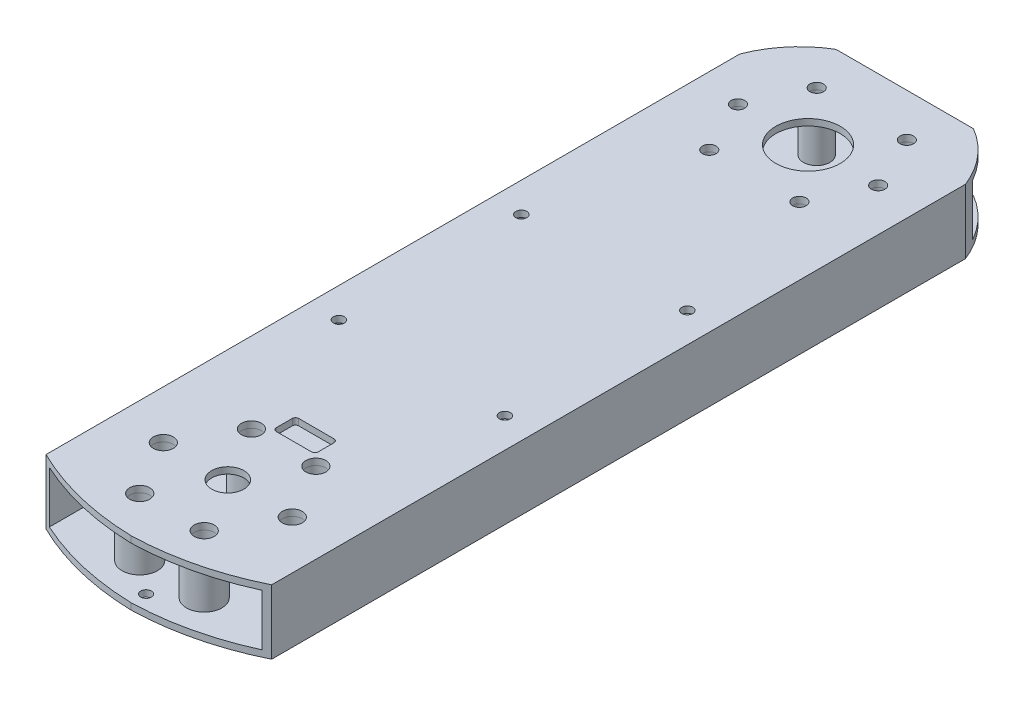
SolidWorks part; units mm, degrees
material "6061-T4 (SS)"
ref_plane "前视基准面" through (0, 0, 0) normal (0, 0, 1) x (1, 0, 0)
ref_plane "上视基准面" through (0, 0, 0) normal (0, 1, 0) x (1, 0, 0)
ref_plane "右视基准面" through (0, 0, 0) normal (1, 0, 0) x (0, 0, -1)
sketch "草图1" plane through (0, 0, 0) normal (0, 0, 1) x (1, 0, 0)
  line L0 (-33, 8) -> (-33, -8)
  line L1 (-35, 10) -> (35, 10)
  line L2 (-35, 10) -> (-35, -10)
  line L3 (-35, -10) -> (35, -10)
  line L4 (35, 10) -> (35, -10)
  line L5 (-35, 10) -> (35, -10) construction
  line L6 (-35, -10) -> (35, 10) construction
  line L7 (-33, -8) -> (33, -8)
  line L8 (33, 8) -> (33, -8)
  line L9 (-33, 8) -> (33, 8)
  point P0 (0, 0)
  dimension "D1" = 20
  dimension "D2" = 70
  dimension "D3" = 2
extrude "凸台-拉伸1" add sketch "草图1" along normal blind 240
sketch "草图2" plane through (0, 10, 0) normal (0, 1, 0) x (1, 0, 0)
  line L0 (35, 0) -> (-35, 0) construction
  circle A0 centre (0, -30) radius 10
  dimension "D1" = 20
  dimension "D2" = 30
extrude "切除-拉伸1" cut sketch "草图2" against normal up to next
sketch "草图3" plane through (0, 10, 0) normal (0, 1, 0) x (1, 0, 0)
  circle A0 centre (0, -210) radius 5
  circle A1 centre (0, -30) radius 10 construction
  dimension "D1" = 180
  dimension "D2" = 10
extrude "切除-拉伸2" cut sketch "草图3" against normal up to next
sketch "草图4" plane through (0, 10, 0) normal (0, 1, 0) x (1, 0, 0)
  line L0 (-13.9806, -13.3385) -> (0, -30) construction
  line L1 (0, -11) -> (0, 11) construction
  line L2 (13.9806, -13.3385) -> (0, -30) construction
  line L3 (0, -30) -> (14.9626, -30) construction
  circle A0 centre (0, -30) radius 21.75 construction
  circle A1 centre (-13.9806, -13.3385) radius 2.1
  circle A2 centre (-21.75, -30) radius 2.1
  circle A3 centre (13.9806, -13.3385) radius 2.1
  circle A4 centre (21.75, -30) radius 2.1
  circle A5 centre (13.9806, -46.6615) radius 2.1
  circle A6 centre (-13.9806, -46.6615) radius 2.1
  dimension "D1" = 43.5
  dimension "D3" = 4.2
  dimension "D2" = 80
extrude "切除-拉伸3" cut sketch "草图4" against normal through all
sketch "草图7" plane through (0, -10, 0) normal (0, -1, 0) x (1, 0, 0)
  line L0 (-35, 240) -> (-35, 0) construction
  line L1 (-35, 0) -> (35, 0) construction
  line L2 (-35, 16.1803) -> (-35, 0)
  line L3 (-35, 0) -> (-21.3082, 0)
  line L4 (0, -11) -> (0, 11) construction
  line L5 (35, 16.1803) -> (35, 0)
  line L6 (35, 0) -> (21.3082, 0)
  arc A0 (-35, 16.1803) -> (-21.3082, 0) centre (-4.9317, 27.741) ccw
  arc A1 (35, 16.1803) -> (21.3082, 0) centre (4.9317, 27.741) cw
extrude "切除-拉伸5" cut sketch "草图7" against normal up to next
sketch "草图10" plane through (0, 10, 0) normal (0, 1, 0) x (1, 0, 0)
  line L0 (-35, -240) -> (-35, -16.1803) construction
  line L1 (35, -240) -> (-35, -240) construction
  line L2 (-35, -231.3969) -> (-35, -240)
  line L3 (-35, -240) -> (35, -240)
  line L4 (0, -11) -> (0, 11) construction
  line L5 (35, -231.3969) -> (35, -240)
  arc A0 (-35, -231.3969) -> (0, -240) centre (2.0788, -156.0456) ccw
  arc A1 (35, -231.3969) -> (0, -240) centre (-2.0788, -156.0456) cw
  line M16 (-35, -16.1803) -> (-35, -240)
  line M17 (-35, -240) -> (35, -240)
  line M18 (35, -240) -> (35, -16.1803)
extrude "切除-拉伸8" cut sketch "草图10" against normal through all contours A0 M16 M17 | A1 L3 M18 region at (-25.9053, 10, 237.4389) region at (25.9053, 10, 237.4389)
sketch "草图13" plane through (0, 10, 0) normal (0, 1, 0) x (1, 0, 0)
  circle A0 centre (0, -210) radius 20 construction
  circle A1 centre (-20, -210) radius 3.1
  circle A2 centre (-10, -192.6795) radius 3.1
  circle A3 centre (10, -192.6795) radius 3.1
  circle A4 centre (20, -210) radius 3.1
  circle A5 centre (10, -227.3205) radius 3.1
  circle A6 centre (-10, -227.3205) radius 3.1
  point P17 (0, -210)
  dimension "D1" = 40
  dimension "D2" = 6.2
  dimension "D3" = 6
extrude "切除-拉伸10" cut sketch "草图13" against normal through all
sketch "草图14" plane through (0, 10, 0) normal (0, 1, 0) x (1, 0, 0)
  line L1 (-6.5, -182.5) -> (6.5, -182.5)
  line L2 (-6.5, -182.5) -> (-6.5, -189.5)
  line L3 (-6.5, -189.5) -> (6.5, -189.5)
  line L4 (6.5, -182.5) -> (6.5, -189.5)
  circle A0 centre (0, -210) radius 5 construction
  point P4 (0, -210)
  point P5 (-6.5, -186)
  point P9 (0, -189.5)
  dimension "D1" = 13
  dimension "D2" = 7
  dimension "D3" = 24
extrude "切除-拉伸11" cut sketch "草图14" against normal up to next
fillet "圆角1" radius 1 4 edges at (6.5, 9, 189.5) (-6.5, 9, 189.5) (6.5, 9, 182.5) (-6.5, 9, 182.5)
ref_axis "基准轴1" through (0, 0, 0) along (0, 0, -1)
sketch "草图15" plane through (0, -10, 0) normal (0, -1, 0) x (1, 0, 0)
  line L0 (-19.4178, 184.3644) -> (-7.8462, 179.841) construction
  line L1 (-7.8462, 179.841) -> (-17.7624, 171.5366) construction
  line L2 (-17.7624, 171.5366) -> (-19.4178, 184.3644) construction
  line L3 (0, 172.4773) -> (-11.4229, 159.2226) construction
  line L4 (-11.4229, 159.2226) -> (-9.9335, 152.7685) construction
  line L5 (-9.9335, 152.7685) -> (9.9335, 152.7685) construction
  line L8 (-16.8218, 85.3147) -> (-13.0628, 86.976) construction
  line L9 (-13.0628, 86.976) -> (-8.8371, 80.5314) construction
  line L10 (-8.8371, 80.5314) -> (-13.9282, 77.1933) construction
  line L11 (-13.9282, 77.1933) -> (-16.8218, 85.3147) construction
  line L12 (0, 76.7339) -> (-13.644, 67.7877) construction
  line L13 (-13.644, 67.7877) -> (0, 55.5925) construction
  line L16 (0, -11) -> (0, 11) construction
  line L17 (7.8462, 179.841) -> (17.7624, 171.5366) construction
  line L18 (19.4178, 184.3644) -> (7.8462, 179.841) construction
  line L19 (17.7624, 171.5366) -> (19.4178, 184.3644) construction
  line L20 (8.8371, 80.5314) -> (13.9282, 77.1933) construction
  line L21 (13.0628, 86.976) -> (8.8371, 80.5314) construction
  line L22 (16.8218, 85.3147) -> (13.0628, 86.976) construction
  line L23 (13.9282, 77.1933) -> (16.8218, 85.3147) construction
  line L24 (13.644, 67.7877) -> (0, 55.5925) construction
  line L25 (0, 76.7339) -> (13.644, 67.7877) construction
  line L26 (11.4229, 159.2226) -> (9.9335, 152.7685) construction
  line L27 (0, 172.4773) -> (11.4229, 159.2226) construction
  circle A0 centre (0, 30) radius 1
  circle A1 centre (0, 30) radius 10 construction
  point P33 (0, 152.7685)
  dimension "D1" = 2
extrude "切除-拉伸12" cut sketch "草图15" against normal up to next
sketch "草图16" plane through (0, -10, 0) normal (0, -1, 0) x (1, 0, 0)
  circle A0 centre (-10, 227.3205) radius 5
  circle A1 centre (10, 227.3205) radius 5
  circle A2 centre (20, 210) radius 5
  circle A3 centre (10, 192.6795) radius 5
  circle A4 centre (-10, 192.6795) radius 5
  circle A5 centre (-20, 210) radius 5
  circle A6 centre (0, 210) radius 1
  dimension "D1" = 10
  dimension "D2" = 2
hole_wizard "M3 螺纹孔1" positions "3D草图1" profile "草图19" tap size "M3" standard "GB" end condition up to next
sketch3d "3D草图1"
  circle A0 centre (0, -10, 30) radius 1 construction
  circle A1 centre (0, -10, 210) radius 1 construction
  point P0 (0, -10, 30)
  point P6 (0, -11, 30)
  point P7 (0, -10, 210)
  point P12 (0, -11, 210)
sketch "草图19" plane through (0, -10, 30) normal (1, 0, 0) x (0, 0, -1)
  line L0 (0, 0) -> (0, 20)
  line L1 (0, 20) -> (1.25, 20)
  line L2 (1.25, 20) -> (1.25, 0)
  line L5 (1.25, 0) -> (0, 0)
  line L11 (0, -6.35) -> (0, 107.95) construction
  dimension "通孔螺纹孔钻头直径" = 2.5
  dimension "通孔螺纹孔钻头深度" = 20
cosmetic thread "孔螺蚊线1" parameters "D2"=3
cosmetic thread "孔螺蚊线2" parameters "D2"=3
ref_axis "基准轴2" through (0, -8, 30) along (0, -1, 0)
ref_plane "基准面1" through (0, 0, 0) normal (1, 0, 0) x (0, -1, 0)
sketch "草图40" plane through (0, -10, 0) normal (0, -1, 0) x (1, 0, 0)
  line L0 (0, -1.1) -> (0, 1.1) construction
  line L1 (-21.3082, 0) -> (21.3082, 0) construction
  circle A0 centre (-4, 20) radius 1.7
  circle A1 centre (4, 20) radius 1.7
  dimension "D1" = 3.4
  dimension "D2" = 8
  dimension "D3" = 20
extrude "切除-拉伸21" cut sketch "草图40" against normal blind 10
sketch "草图45" plane through (35, 0, 0) normal (1, 0, 0) x (0, 0, -1)
  line L0 (-231, 8) -> (-204, -10)
  line L2 (-240, 8) -> (-240, 10) construction
  line L3 (-240, -10) -> (-240, -8) construction
  line L4 (-240, 8) -> (-231, 8)
  line L5 (-204, -10) -> (-240, -10)
  line L6 (-240, -10) -> (-240, 8)
  dimension "D1" = 9
  dimension "D2" = 36
extrude "偷轻" [suppressed] cut sketch "草图45" against normal through all
sketch "草图46" [suppressed] plane through (0, -10, 0) normal (0, -1, 0) x (-1, 0, 0)
  line L0 (33, -207) -> (11.9465, -187.6795)
  line L1 (11.9465, -187.6795) -> (-11.9465, -187.6795)
  line L2 (-11.9465, -187.6795) -> (-33, -207)
  line L3 (35, -204) -> (-35, -204) construction
  line L4 (33, -207) -> (-33, -207)
  circle A0 centre (-10, -192.6795) radius 5 construction
  circle A1 centre (-10, -192.6795) radius 5 construction
  circle A2 centre (10, -192.6795) radius 5 construction
  circle A3 centre (10, -192.6795) radius 5 construction
  point P9 (0, -204)
  point P10 (0, -187.6795)
extrude "切除-拉伸26" [suppressed] cut sketch "草图46" against normal up to next
fillet "圆角5" [suppressed] radius 6
sketch "草图49" plane through (0, 8, 0) normal (0, -1, 0) x (1, 0, 0)
  line L0 (0, -1.1) -> (0, 1.1) construction
  circle A0 centre (-13.9806, 46.6615) radius 4.1
  circle A1 centre (-13.9806, 46.6615) radius 2.2
  circle A2 centre (-21.75, 30) radius 2.2
  circle A3 centre (-21.75, 30) radius 4.1
  circle A4 centre (-13.9806, 13.3385) radius 4.1
  circle A5 centre (-13.9806, 13.3385) radius 2.2
  circle A6 centre (13.9806, 13.3385) radius 2.2
  circle A7 centre (13.9806, 13.3385) radius 4.1
  circle A8 centre (21.75, 30) radius 4.1
  circle A9 centre (21.75, 30) radius 2.2
  circle A10 centre (13.9806, 46.6615) radius 2.2
  circle A11 centre (13.9806, 46.6615) radius 4.1
  circle A12 centre (-10, 227.3205) radius 3.2
  circle A13 centre (-10, 227.3205) radius 5.5
  circle A14 centre (10, 227.3205) radius 5.5
  circle A15 centre (10, 227.3205) radius 3.2
  circle A16 centre (20, 210) radius 5.5
  circle A17 centre (20, 210) radius 3.2
  circle A18 centre (10, 192.6795) radius 5.5
  circle A19 centre (10, 192.6795) radius 3.2
  circle A20 centre (-10, 192.6795) radius 5.5
  circle A21 centre (-10, 192.6795) radius 3.2
  circle A22 centre (-20, 210) radius 5.5
  circle A23 centre (-20, 210) radius 3.2
  circle A24 centre (10, 227.3205) radius 3.1 construction
  point P44 (0, 210)
  dimension "D1" = 4.4
  dimension "D2" = 8.2
  dimension "D3" = 6.4
  dimension "D4" = 11
  dimension "D5" = 6
extrude "凸台-拉伸2" add sketch "草图49" along normal up to surface (16 mm away) up to face at (-4, -8, 21.7)
sketch "草图50" plane through (0, 10, 0) normal (0, 1, 0) x (1, 0, 0)
  circle A0 centre (-25.75, -93.2) radius 1.7
  circle A1 centre (25.75, -93.2) radius 1.7
  circle A2 centre (-25.75, -149.8) radius 1.7
  circle A3 centre (25.75, -149.8) radius 1.7
  dimension "D1" = 3.4
extrude "切除-拉伸27" cut sketch "草图50" against normal blind 2
sketch "草图51" plane through (0, -10, 0) normal (0, -1, 0) x (1, 0, 0)
  line L0 (-29, 93) -> (-29, 150) construction
  line L1 (-11, 88) -> (-29, 88)
  line L2 (-11, 88) -> (-11, 153)
  line L3 (-11, 153) -> (-29, 153)
  line L4 (-29, 88) -> (-29, 153)
  line L5 (26, 90) -> (-26, 90) construction
  line L6 (-26, 153) -> (26, 153) construction
  dimension "D1" = 2
  dimension "D2" = 18
extrude "切除-拉伸28" cut sketch "草图51" against normal blind 2
fillet "圆角6" radius 3 4 edges at (-11, -9, 153) (-29, -9, 153) (-29, -9, 88) (-11, -9, 88)
sketch "草图52" plane through (0, -10, 0) normal (0, -1, 0) x (1, 0, 0)
  line L0 (0, -11) -> (0, 11) construction
  line L1 (-24, 168.7886) -> (-24, 78.7886) construction
  line L2 (-35, 231.3969) -> (-35, 16.1803) construction
  circle A0 centre (-24, 168.7886) radius 1.3
  circle A1 centre (-24, 78.7886) radius 1.3
  circle A2 centre (24, 78.7886) radius 1.3
  circle A3 centre (24, 168.7886) radius 1.3
  point P6 (-35, 123.7886)
  point P7 (-24, 123.7886)
  dimension "D1" = 2.6
  dimension "D2" = 48
  dimension "D3" = 90
extrude "切除-拉伸29" cut sketch "草图52" against normal up to next
sketch "草图53" plane through (0, -10, 0) normal (0, -1, 0) x (1, 0, 0)
  circle A0 centre (0, 235.3485) radius 1.65
  arc A1 (35, 231.3969) -> (0, 240) centre (-2.0788, 156.0456) ccw construction
  point P6 (0, 210)
  dimension "D1" = 3
  dimension "D2" = 3.3
extrude "切除-拉伸30" cut sketch "草图53" against normal up to next
